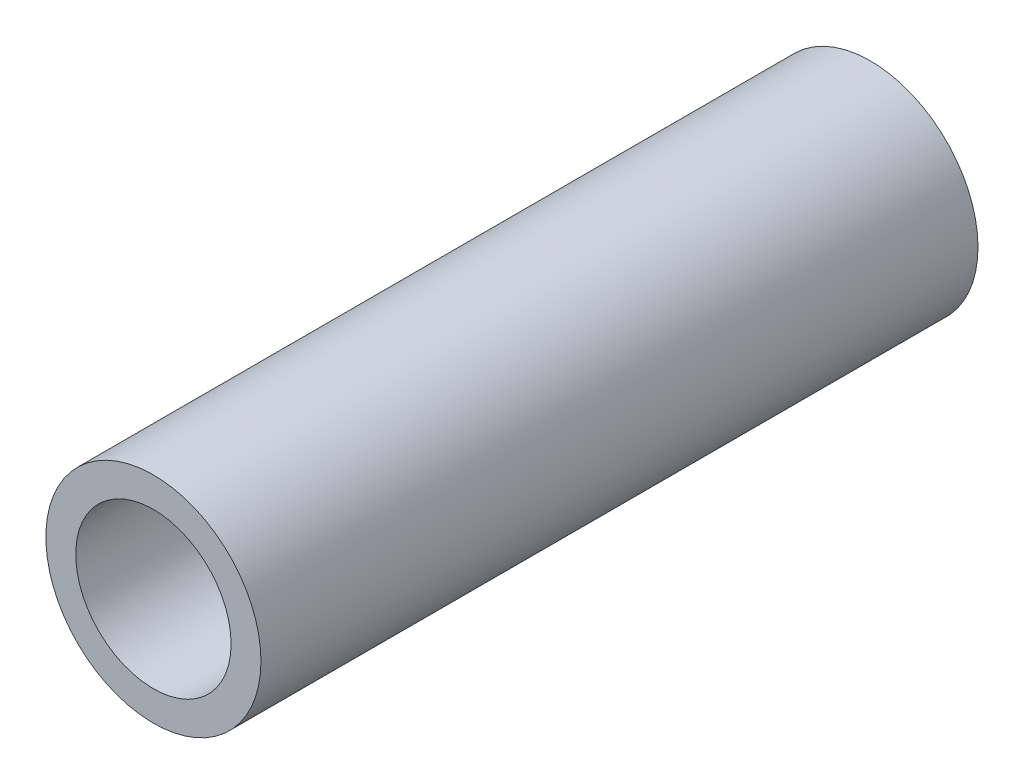
SolidWorks part; units mm, degrees
ref_plane "Front Plane" through (0, 0, 0) normal (0, 0, 1) x (1, 0, 0)
ref_plane "Top Plane" through (0, 0, 0) normal (0, 1, 0) x (1, 0, 0)
ref_plane "Right Plane" through (0, 0, 0) normal (1, 0, 0) x (0, 0, -1)
sketch "Sketch1" plane through (0, 0, 0) normal (0, 0, 1) x (1, 0, 0)
  circle A0 centre (0, 0) radius 9
  circle A2 centre (0, 0) radius 6.5
extrude "Boss-Extrude1" add sketch "Sketch1" along normal blind 30 and the other way blind 30
